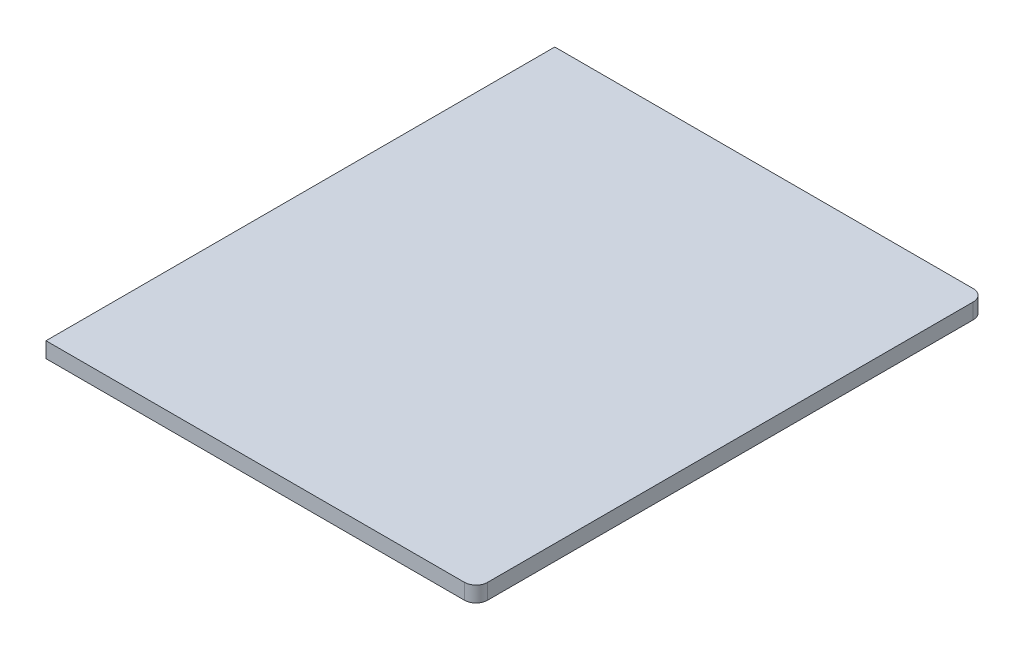
SolidWorks part; units mm, degrees
ref_plane "Front Plane" through (0, 0, 0) normal (0, 0, 1) x (1, 0, 0)
ref_plane "Top Plane" through (0, 0, 0) normal (0, 1, 0) x (1, 0, 0)
ref_plane "Right Plane" through (0, 0, 0) normal (1, 0, 0) x (0, 0, -1)
sketch "Sketch1" plane through (0, 0, 0) normal (0, 1, 0) x (1, 0, 0)
  line L0 (-124.873, 0) -> (36.3874, 0) construction
  line L1 (-67.4844, 44.0676) -> (-67.4844, 13.2939) construction
  line L2 (-107, -60.9298) -> (-5, -60.9298) construction
  line L3 (-107, -60.9298) -> (-107, 60.9298) construction
  line L4 (-107, 60.9298) -> (-5, 60.9298) construction
  line L5 (-5, -60.9298) -> (-5, 60.9298) construction
  line L6 (-107, -60.9298) -> (-5, 60.9298) construction
  line L7 (-107, 60.9298) -> (-5, -60.9298) construction
  line L8 (-112, -65.9298) -> (-112, 65.9298)
  line L9 (-60.2, -7.05) -> (-46.1, -7.05) construction
  line L10 (-60.2, -7.05) -> (-60.2, 7.05) construction
  line L11 (-60.2, 7.05) -> (-46.1, 7.05) construction
  line L12 (-46.1, -7.05) -> (-46.1, 7.05) construction
  line L13 (-60.2, -7.05) -> (-46.1, 7.05) construction
  line L14 (-60.2, 7.05) -> (-46.1, -7.05) construction
  line L19 (-112, 65.9298) -> (0, 65.9298)
  line L20 (0, -65.9298) -> (0, 65.9298)
  line L21 (-112, -65.9298) -> (0, -65.9298)
  line L22 (-62.7, -9.55) -> (-62.7, 9.55) construction
  line L31 (-9.5, -9.55) -> (-28.6, -9.55) construction
  line L32 (-36.1, 26.444) -> (-26.1298, 36.4142) construction
  line L33 (-62.7, 9.55) -> (-43.6, 9.55) construction
  line L34 (-43.6, -9.55) -> (-43.6, 9.55) construction
  line L35 (-62.7, -9.55) -> (-43.6, -9.55) construction
  line L36 (-36.1, 79.1779) -> (-36.1, -87.4984) construction
  line L41 (-36.1, 26.444) -> (-46.0702, 36.4142) construction
  line L42 (-46.0702, 36.4142) -> (-36.1, 46.3844) construction
  line L43 (-26.1298, 36.4142) -> (-36.1, 46.3844) construction
  line L44 (-36.1, 26.444) -> (-36.1, 46.3844) construction
  line L45 (-46.0702, 36.4142) -> (-26.1298, 36.4142) construction
  line L46 (-28.6, -9.55) -> (-28.6, 9.55) construction
  line L47 (-9.5, 9.55) -> (-28.6, 9.55) construction
  line L48 (-9.5, -9.55) -> (-9.5, 9.55) construction
  line L49 (-12, 7.05) -> (-26.1, 7.05) construction
  line L50 (-26.1, -7.05) -> (-26.1, 7.05) construction
  line L51 (-12, -7.05) -> (-26.1, -7.05) construction
  line L52 (-12, -7.05) -> (-12, 7.05) construction
  line L53 (-43.6, -3.1311) -> (-28.6, -3.1311) construction
  line L54 (-82.4844, 60.9298) -> (-82.4844, 36.4142) construction
  line L55 (-9.5, 4.2306) -> (5.5, 4.2306) construction
  line L56 (-43.15, -36.15) -> (-29.05, -36.15) construction
  line L57 (-43.15, -36.15) -> (-43.15, -22.05) construction
  line L58 (-43.15, -22.05) -> (-29.05, -22.05) construction
  line L59 (-29.05, -36.15) -> (-29.05, -22.05) construction
  line L60 (-43.15, -36.15) -> (-29.05, -22.05) construction
  line L61 (-43.15, -22.05) -> (-29.05, -36.15) construction
  line L62 (-55.2, -38.65) -> (-17, -38.65) construction
  line L63 (-55.2, -38.65) -> (-55.2, -19.55) construction
  line L64 (-55.2, -19.55) -> (-17, -19.55) construction
  line L65 (-17, -38.65) -> (-17, -19.55) construction
  line L66 (-55.2, -38.65) -> (-17, -19.55) construction
  line L67 (-55.2, -19.55) -> (-17, -38.65) construction
  line L68 (-82.4844, 36.4142) -> (-107, 36.4142) construction
  line L69 (-87.8844, 35.1642) -> (-77.0844, 35.1642) construction
  line L70 (-87.8844, 35.1642) -> (-87.8844, 37.6642) construction
  line L71 (-87.8844, 37.6642) -> (-77.0844, 37.6642) construction
  line L72 (-77.0844, 35.1642) -> (-77.0844, 37.6642) construction
  line L73 (-87.8844, 35.1642) -> (-77.0844, 37.6642) construction
  line L74 (-87.8844, 37.6642) -> (-77.0844, 35.1642) construction
  line L75 (-82.4844, 0) -> (-82.4844, 36.4142) construction
  line L76 (-82.4844, 36.4142) -> (-46.0702, 36.4142) construction
  line L77 (-36.1, 25.0298) -> (-47.4844, 36.4142) construction
  line L78 (-47.4844, 36.4142) -> (-36.1, 47.7986) construction
  line L79 (-24.7156, 36.4142) -> (-36.1, 47.7986) construction
  line L80 (-36.1, 25.0298) -> (-24.7156, 36.4142) construction
  line L81 (-112, 63.8298) -> (-2.1, 63.8298)
  line L82 (-112, 65.9298) -> (-110, 65.9298)
  line L83 (-112, 65.9298) -> (-112, -65.9298)
  line L84 (-112, -65.9298) -> (-110, -65.9298)
  line L85 (-110, 65.9298) -> (-110, -65.9298)
  line L86 (-2.1, -63.8298) -> (-2.1, 63.8298)
  line L87 (-112, -63.8298) -> (-2.1, -63.8298)
  line L88 (-2, 65.9298) -> (-2, -65.9298) construction
  circle A0 centre (-82.4844, 36.4142) radius 4.175 construction
  circle A1 centre (-82.4844, 36.4142) radius 15 construction
  circle A5 centre (-5, 60.9298) radius 2.9
  circle A6 centre (-5, -60.9298) radius 2.9
  circle A7 centre (-107, 60.9298) radius 2.1
  circle A8 centre (-5, 60.9298) radius 2.1
  circle A9 centre (-5, -60.9298) radius 2.1
  circle A10 centre (-107, -60.9298) radius 2.1
  point P3 (-56, 0)
  point P8 (-53.15, 0)
  point P21 (-36.1, 36.4142)
  point P26 (-36.1, -29.1)
  point P49 (-36.1, -29.1)
  point P69 (6.661, 4.2838)
  point P81 (-4.0038, 67.9298)
  point P82 (-2, 4.2306)
  dimension "D11" = 8.35
  dimension "D14" = 30
  dimension "D17" = 4.2
  dimension "D4" = 14.1
  dimension "D3" = 2.5
  dimension "D5" = 19.1
  dimension "D6" = 38.2
  dimension "D7" = 10
  dimension "D8" = 15
  dimension "D12" = 2.5
  dimension "D13" = 10.8
  dimension "D15" = 20
  dimension "D16" = 2
  dimension "D10" = 110
  dimension "D19" = 2
  dimension "D1" = 5
  dimension "D2" = 2.5
  dimension "D9" = 1
  dimension "D18" = 2.1
extrude "Boss-Extrude1" add sketch "Sketch1" along normal blind 3.9 contours A6 L86 A5 L81 L85 L87 A10 A7 | A5 A8 | A6 A9 | A7 | A8 | A10 | A9 region at (-56.158, 0, 0) region at (-6.9926, 0, 58.9372) region at (-3.0074, 0, -62.9224) region at (-107, 0, -60.9298) region at (-5, 0, -60.9298) region at (-5, 0, 60.9298) region at (-107, 0, 60.9298)
extrude "Cut-Extrude1" cut sketch "Sketch1<6>" along normal blind 1.6 contours A8 | A9 | A7 | A10 region at (-107, 0, -60.9298) region at (-5, 0, -60.9298) region at (-5, 0, 60.9298) region at (-107, 0, 60.9298)
sketch "Sketch1<6>" plane through (0, 0, 0) normal (0, 1, 0) x (1, 0, 0) same geometry as "Sketch1"
equation "\"Magnet Hole Dia\"= 4.2"
equation "\"Keyswitch Hole L\" = 14.1"
equation "\"Dial Hole Dia\" = 8.35"
equation "\"Dial Hole Rec L\"= 10.8"
equation "\"Dial Hole Rec W\"= 2.5"
equation "\"Wall Thickness\"= 5"
equation "\"Magnet Hole Depth\"= 1.6"
equation "\"Tape Hole L\"= 6"
equation "\"Tape Hole W\"= 2"
equation "\"D17@Sketch1\"=\"Magnet Hole Dia\""
equation "\"D1@Cut-Extrude1\"=\"Magnet Hole Depth\""
equation "\"D11@Sketch1\"=\"Dial Hole Dia\""
equation "\"D13@Sketch1\"=\"Dial Hole Rec L\""
equation "\"D12@Sketch1\"=\"Dial Hole Rec W\""
equation "\"D4@Sketch1\"=\"Keyswitch Hole L\""
equation "\"D1@Sketch1\"=\"Wall Thickness\""
